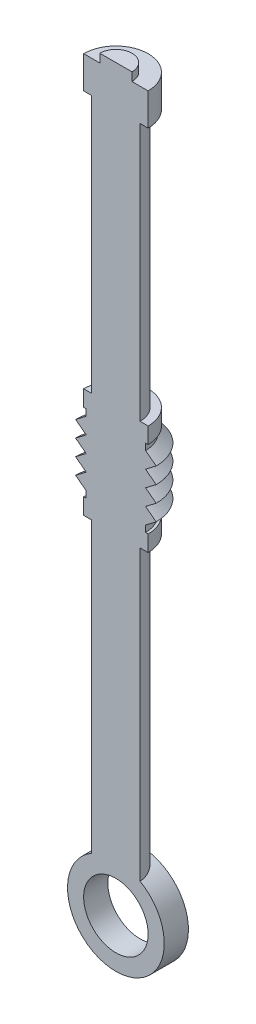
SolidWorks part; units mm, degrees
ref_plane "Front Plane" through (0, 0, 0) normal (0, 0, 1) x (1, 0, 0)
ref_plane "Top Plane" through (0, 0, 0) normal (0, 1, 0) x (1, 0, 0)
ref_plane "Right Plane" through (0, 0, 0) normal (1, 0, 0) x (0, 0, -1)
sketch "Sketch1" plane through (0, 0, 0) normal (0, 0, 1) x (1, 0, 0)
  circle A0 centre (0, 0) radius 3.175
  circle A1 centre (0, 0) radius 4.7625
  dimension "D1" = 6.35
  dimension "D2" = 1.5875
extrude "Boss-Extrude1" add sketch "Sketch1" along normal blind 4.7625 and the other way blind 2.3813
ref_plane "Plane1" through (0, 4.7625, 0) normal (0, 1, 0) x (1, 0, 0)
sketch "Sketch2" plane through (0, 4.7625, 0) normal (0, 1, 0) x (1, 0, 0)
  line L1 (4.7625, 2.3813) -> (-4.7625, 2.3813) construction
  circle A0 centre (0, 0) radius 2.3813
  dimension "D1" = 4.7625
extrude "Boss-Extrude2" add sketch "Sketch2" along normal blind 28.575 and the other way up to surface other way up to face at (4.7625, 0, -2.3813)
sketch "Sketch3" plane through (0, 0, 0) normal (1, 0, 0) x (0, 0, -1)
  line L0 (-2.921, 34.1313) -> (-2.921, 34.7662)
  line L1 (0, 32.5438) -> (-3.175, 32.5438)
  line L2 (0, 32.5438) -> (0, 34.1313)
  line L3 (0, 34.1313) -> (-3.175, 34.1313)
  line L4 (-3.175, 32.5438) -> (-3.175, 34.1313)
  line L5 (-2.921, 34.7662) -> (-3.9688, 35.56)
  line L6 (-3.9688, 35.56) -> (-2.921, 36.3537)
  line L7 (2.3813, 33.3375) -> (-2.3813, 33.3375) construction
  line L8 (-2.3813, 33.3375) -> (-2.3813, 4.7625) construction
  line L9 (-2.3813, 33.3375) -> (-2.3813, 4.7625) construction
  line L10 (-2.921, 36.3537) -> (-3.9688, 37.1475)
  line L11 (-3.9688, 37.1475) -> (-2.921, 37.9412)
  line L12 (-2.921, 37.9412) -> (-3.9688, 38.735)
  line L13 (-3.9688, 38.735) -> (-2.921, 39.5287)
  line L14 (-2.921, 39.5287) -> (-3.9687, 40.3225)
  line L15 (-3.9687, 40.3225) -> (-2.921, 41.1162)
  line L16 (-2.921, 41.1162) -> (-2.921, 41.7512)
  line L17 (-2.921, 41.7512) -> (-3.175, 41.7512)
  line L18 (-3.175, 41.7512) -> (-3.175, 43.3387)
  line L19 (-3.175, 43.3387) -> (0, 43.3387)
  line L20 (0, 43.3387) -> (0, 34.1313)
  line L21 (0, 34.1313) -> (0.014, 34.1171)
  dimension "D1" = 0.635
  dimension "D2" = 1.5875
  dimension "D3" = 0.7937
  dimension "D4" = 0.7937
  dimension "D5" = 2.3813
  dimension "D6" = 1.5875
  dimension "D7" = 0.7937
  dimension "D8" = 0.254
  dimension "D9" = 0.7937
  dimension "D10" = 1.5875
revolve "Revolve1" add sketch "Sketch3" angle 360 about L2 region at (0, 38.6989, 1.678) region at (0, 33.3375, 1.5875)
sketch "Sketch4" plane through (0, 43.3387, 0) normal (0, 1, 0) x (1, 0, 0)
  circle A0 centre (0, 0) radius 2.3813
  dimension "D1" = 4.7625
extrude "Boss-Extrude3" add sketch "Sketch4" along normal blind 25.4
sketch "Sketch5" plane through (0, 68.7387, 0) normal (0, 1, 0) x (1, 0, 0)
  circle A0 centre (0, 0) radius 3.175
  dimension "D1" = 6.35
extrude "Boss-Extrude4" add sketch "Sketch5" along normal blind 3.175
sketch "Sketch6" plane through (0, 71.9137, 0) normal (0, 1, 0) x (1, 0, 0)
  circle A0 centre (0, 0) radius 1.5875
  dimension "D1" = 3.175
extrude "Boss-Extrude5" add sketch "Sketch6" along normal blind 0.8318
sketch "Sketch7" plane through (0, 0, 0) normal (0, 0, 1) x (1, 0, 0)
  line L1 (-7.1402, 75.337) -> (8.3945, 75.337)
  line L2 (-7.1402, 75.337) -> (-7.1402, -6.4855)
  line L3 (-7.1402, -6.4855) -> (8.3945, -6.4855)
  line L4 (8.3945, 75.337) -> (8.3945, -6.4855)
extrude "Cut-Extrude1" cut sketch "Sketch7" along normal through all
